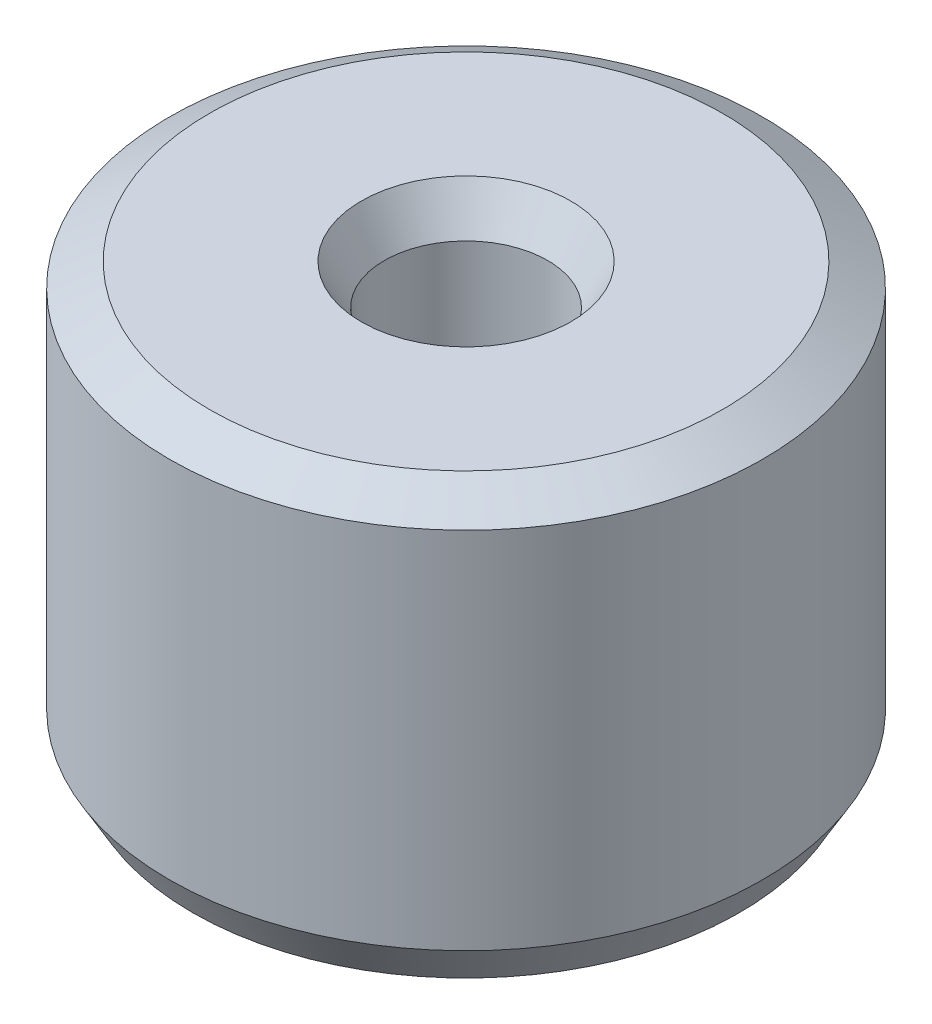
SolidWorks part; units mm, degrees
ref_plane "Front Plane" through (0, 0, 0) normal (0, 0, 1) x (1, 0, 0)
ref_plane "Top Plane" through (0, 0, 0) normal (0, 1, 0) x (1, 0, 0)
ref_plane "Right Plane" through (0, 0, 0) normal (1, 0, 0) x (0, 0, -1)
sketch "Sketch1" plane through (0, 0, 0) normal (0, 1, 0) x (1, 0, 0)
  circle A0 centre (0, 0) radius 5
  dimension "SLEEVE_OD" = 10
extrude "Boss-Extrude1" add sketch "Sketch1" along normal blind 7.2028
sketch "Sketch2" plane through (0, 0, 0) normal (0, 1, 0) x (1, 0, 0)
  circle A0 centre (0, 0) radius 1.3767
  dimension "BORE_D" = 2.7533
extrude "Cut-Extrude1" cut sketch "Sketch2" along normal through all
chamfer "Chamfer1" distance 0.3893 angle 60 4 edges at (0, 7.2028, 1.3767) (0, 0, 1.3767) (0, 0, 5) (0, 7.2028, 5) first distance on face at (0, 7.2028, 1.3767) first distance on face at (0, 0, 1.3767) first distance on face at (0, 7.2028, 5)
